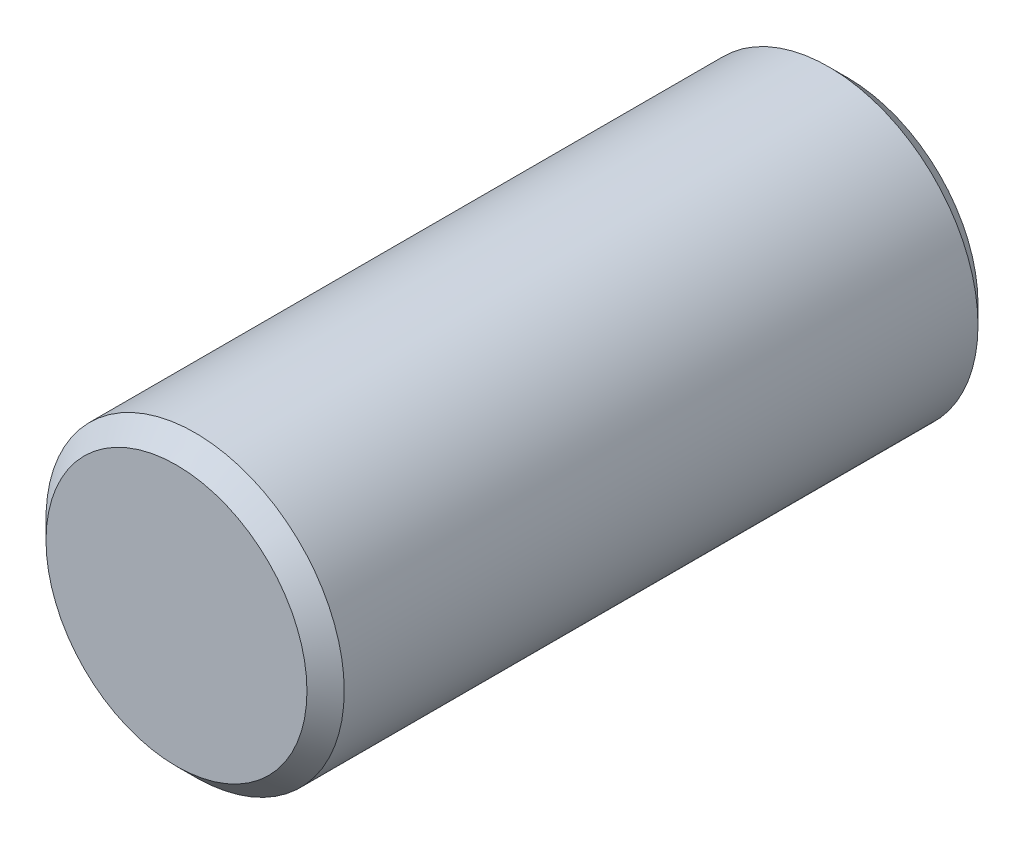
SolidWorks part; units mm, degrees
ref_plane "Front Plane" through (0, 0, 0) normal (0, 0, 1) x (1, 0, 0)
ref_plane "Top Plane" through (0, 0, 0) normal (0, 1, 0) x (1, 0, 0)
ref_plane "Right Plane" through (0, 0, 0) normal (1, 0, 0) x (0, 0, -1)
sketch "Sketch1" plane through (0, 0, 0) normal (0, 0, 1) x (1, 0, 0)
  circle A0 centre (0, 0) radius 4
  dimension "D1" = 8
extrude "Boss-Extrude1" add sketch "Sketch1" along normal blind 9 and the other way blind 9
chamfer "Chamfer1" distance 0.5 angle 45 2 edges at (4, 0, -9) (4, 0, 9)
ref_point "Point1"
ref_point "Point2"
